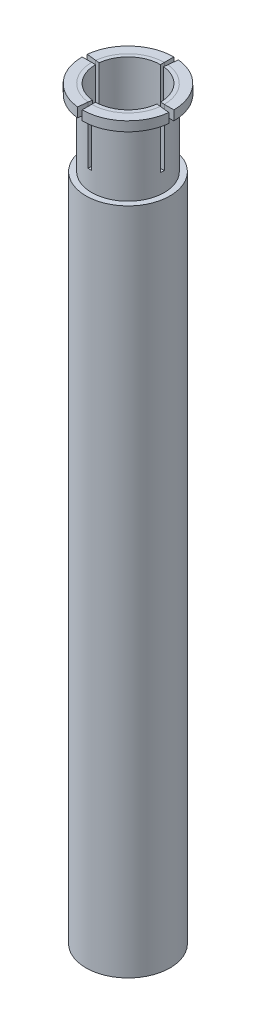
SolidWorks part; units mm, degrees
ref_plane "前视基准面" through (0, 0, 0) normal (0, 0, 1) x (1, 0, 0)
ref_plane "上视基准面" through (0, 0, 0) normal (0, 1, 0) x (1, 0, 0)
ref_plane "右视基准面" through (0, 0, 0) normal (1, 0, 0) x (0, 0, -1)
sketch "草图1" plane through (0, 0, 0) normal (0, 1, 0) x (1, 0, 0)
  circle A0 centre (0, 0) radius 17
  dimension "D1" = 34
extrude "拉伸-薄壁1" add sketch "草图1" along normal blind 50 thin thin type one direction wall 2
cosmetic thread "装饰螺纹线2" parameters "D1"=40, "D2"=36
sketch "草图3" plane through (0, 50, 0) normal (0, 1, 0) x (1, 0, 0)
  line L0 (0, 0) -> (0, 19)
  line L1 (0, 19) -> (2, 19)
  line L2 (2, 19) -> (0, 0)
  circle A0 centre (0, 0) radius 19 construction
  dimension "D1" = 2
extrude "切除-拉伸1" cut sketch "草图3" against normal blind 30
pattern_circular "阵列(圆周)1" count 4 over 360 about axis through (0, 50, 0) along (0, -1, 0) of "切除-拉伸1" reverse direction yes
sketch "草图4" plane through (0, 50, 0) normal (0, 1, 0) x (1, 0, 0)
  line L0 (0, 19) -> (0, 24)
  line L1 (1.989, 18.8956) -> (2.5124, 23.8681)
  line L2 (19, 0) -> (24, 0)
  line L3 (18.8956, -1.989) -> (23.8681, -2.5124)
  line L4 (0, -19) -> (0, -24)
  line L5 (-1.989, -18.8956) -> (-2.5124, -23.8681)
  line L6 (-19, 0) -> (-24, 0)
  line L7 (-18.8956, 1.989) -> (-23.8681, 2.5124)
  arc A0 (0, 19) -> (-18.8956, 1.989) centre (0, 0) ccw
  arc A1 (0, 24) -> (-23.8681, 2.5124) centre (0, 0) ccw
  arc A2 (-19, 0) -> (-1.989, -18.8956) centre (0, 0) ccw
  arc A3 (-24, 0) -> (-2.5124, -23.8681) centre (0, 0) ccw
  arc A4 (19, 0) -> (1.989, 18.8956) centre (0, 0) ccw
  arc A5 (24, 0) -> (2.5124, 23.8681) centre (0, 0) ccw
  arc A6 (0, -19) -> (18.8956, -1.989) centre (0, 0) ccw
  arc A7 (0, -24) -> (23.8681, -2.5124) centre (0, 0) ccw
  point P26 (0, 0)
  dimension "D1" = 48
  dimension "D2" = 4
extrude "凸台-拉伸1" add sketch "草图4" against normal blind 5 separate body
ref_plane "基准面1" through (0, 10, 0) normal (0, 1, 0) x (1, 0, 0)
sketch "草图6" plane through (0, 10, 0) normal (0, 1, 0) x (1, 0, 0)
  circle A0 centre (0, 0) radius 20
  circle A1 centre (0, 0) radius 22
  dimension "D1" = 40
  dimension "D2" = 44
extrude "凸台-拉伸3" add sketch "草图6" against normal blind 350
sketch "草图7" plane through (0, 10, 0) normal (0, 1, 0) x (1, 0, 0)
  circle A1 centre (0, 0) radius 20
  circle A2 centre (0, 0) radius 19
  dimension "D1" = 40
  dimension "D2" = 38
extrude "凸台-拉伸4" add sketch "草图7" against normal up to surface (10 mm away) up to face at (19, 0, 0)
